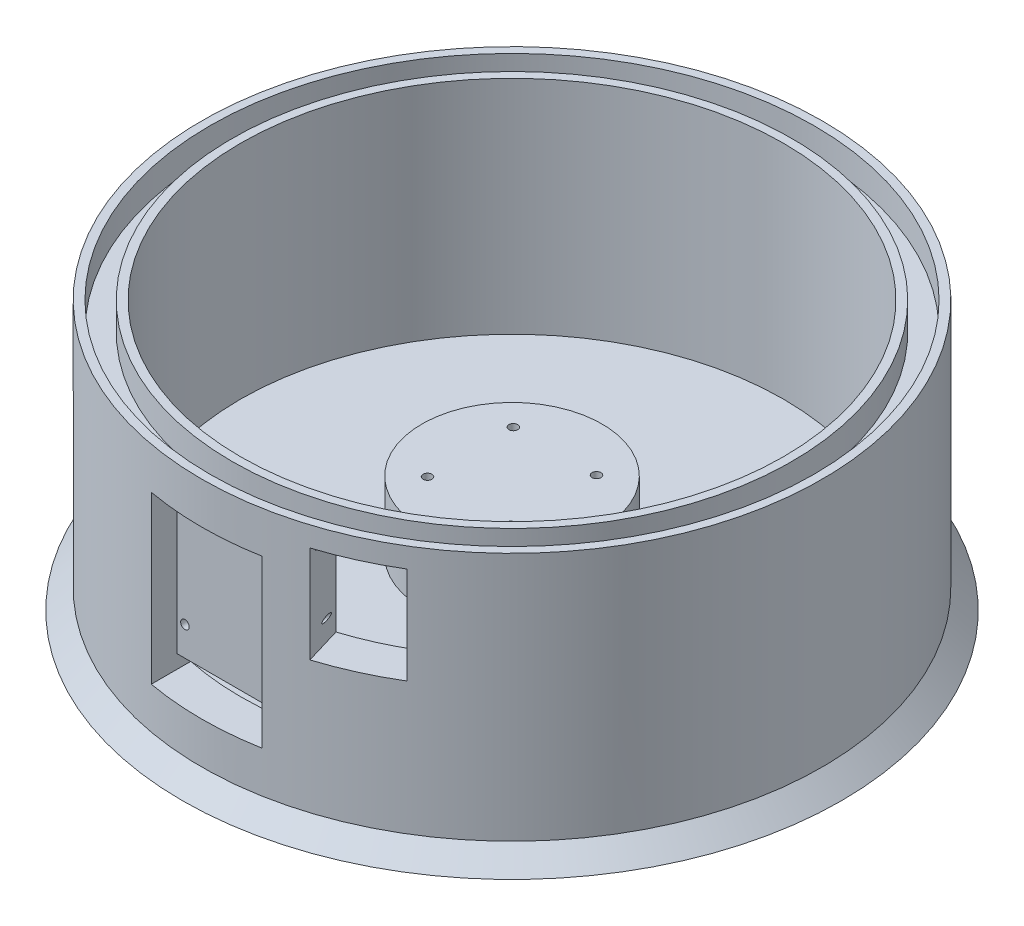
SolidWorks part; units mm, degrees
material "ABS"
ref_plane "Front Plane" through (0, 0, 0) normal (0, 0, 1) x (1, 0, 0)
ref_plane "Top Plane" through (0, 0, 0) normal (0, 1, 0) x (1, 0, 0)
ref_plane "Right Plane" through (0, 0, 0) normal (1, 0, 0) x (0, 0, -1)
sketch "Sketch1" plane through (0, 0, 0) normal (0, 1, 0) x (1, 0, 0)
  circle A1 centre (0, 0) radius 112
extrude "Boss-Extrude3" add sketch "Sketch1" along normal blind 90
ref_plane "Plane1" through (0, 0, 105) normal (0, 0, 1) x (1, 0, 0)
sketch "Sketch9" plane through (0, 90, 0) normal (0, 1, 0) x (1, 0, 0)
  circle A5 centre (0, 0) radius 101
  circle A7 centre (0, 0) radius 109
extrude "Cut-Extrude6" cut sketch "Sketch9" against normal blind 10
sketch "Sketch4" plane through (0, 0, 105) normal (0, 0, 1) x (1, 0, 0)
  line L26 (-20, 75) -> (20, 75)
  line L27 (-20, 75) -> (-20, 15)
  line L28 (-20, 15) -> (20, 15)
  line L29 (20, 75) -> (20, 15)
  line L30 (-20, 75) -> (20, 15) construction
  line L31 (-20, 15) -> (20, 75) construction
  point P0 (-0.4597, 42.5864)
  point P5 (0, 45)
  dimension "D1" = 60
  dimension "D2" = 40
  dimension "D3" = 45
extrude "Cut-Extrude2" cut sketch "Sketch4" along normal blind 26 and the other way blind 4
sketch "Sketch12" plane through (0, 0, 0) normal (0, -1, 0) x (1, 0, 0)
  circle A1 centre (0, 0) radius 112
  circle A2 centre (0, 0) radius 112
  dimension "D1" = 0
extrude "Boss-Extrude4" add sketch "Sketch12" along normal blind 7 draft 45 draft outward yes
sketch "Sketch13" plane through (0, 90, 0) normal (0, 1, 0) x (1, 0, 0)
  circle A0 centre (0, 0) radius 98
extrude "Cut-Extrude8" cut sketch "Sketch13" against normal blind 80 contours A0
sketch "Sketch14" plane through (0, 0, 101) normal (0, 0, 1) x (1, 0, 0)
  circle A0 centre (-31.25, 55.25) radius 0.75
  circle A1 centre (31.25, 55.25) radius 0.75
  circle A2 centre (31.25, 7.75) radius 0.75
  circle A3 centre (-31.25, 7.75) radius 0.75
extrude "Cut-Extrude9" cut sketch "Sketch14" against normal blind 15
sketch "Sketch18" plane through (0, 10, 0) normal (0, 1, 0) x (1, 0, 0)
  circle A0 centre (0, 0) radius 32.5
  dimension "D1" = 65
extrude "Boss-Extrude5" add sketch "Sketch18" along normal blind 25
sketch "Sketch16" plane through (0, -7, 0) normal (0, -1, 0) x (1, 0, 0)
  line L0 (0, 0) -> (-8.9936, 0) construction
  line L1 (0, 0) -> (0, 9.8047) construction
  circle A2 centre (-15, 15.5) radius 1.6
  circle A5 centre (15, 15.5) radius 1.6
  circle A6 centre (15, -15.5) radius 1.6
  circle A7 centre (-15, -15.5) radius 1.6
  point P2 (0, 0)
  dimension "D3" = 3.2
  dimension "D1" = 15.5
  dimension "D2" = 15
extrude "Cut-Extrude11" cut sketch "Sketch16" against normal through all
sketch "Sketch17" plane through (0, -7, 0) normal (0, -1, 0) x (1, 0, 0)
  circle A0 centre (-15, 15.5) radius 3
  circle A1 centre (15, 15.5) radius 3
  circle A2 centre (-15, -15.5) radius 3
  circle A3 centre (15, -15.5) radius 3
  dimension "D1" = 6
  dimension "D2" = 6
  dimension "D3" = 6
  dimension "D4" = 6
extrude "Cut-Extrude12" cut sketch "Sketch17" against normal blind 30
sketch "Sketch19" plane through (0, -7, 0) normal (0, -1, 0) x (1, 0, 0)
  circle A0 centre (0, 0) radius 30
  dimension "D1" = 60
extrude "Cut-Extrude13" cut sketch "Sketch19" against normal blind 25 contours A0
sketch "Sketch20" plane through (0, 0, 101) normal (0, 0, 1) x (1, 0, 0)
  line L0 (20, 75) -> (20, 15) construction
  line L1 (-20, 15) -> (20, 15)
  line L2 (-20, 15) -> (-20, 20)
  line L3 (-20, 20) -> (20, 20)
  line L4 (20, 15) -> (20, 20)
  dimension "D1" = 5
extrude "Cut-Extrude14" cut sketch "Sketch20" against normal blind 25
sketch "Sketch21" plane through (0, 0, 101) normal (0, 0, 1) x (1, 0, 0)
  line L0 (20, 75) -> (-20, 75) construction
  circle A0 centre (12.45, 67.8) radius 1.55
  circle A1 centre (-12.45, 67.8) radius 1.55
  circle A2 centre (-17.05, 30.54) radius 1.55
  circle A3 centre (17.05, 30.54) radius 1.55
  dimension "D3" = 3.1
  dimension "D4" = 3.1
  dimension "D9" = 3.1
  dimension "D10" = 3.1
  dimension "D1" = 12.45
  dimension "D2" = 24.9
  dimension "D5" = 7.2
  dimension "D6" = 7.2
  dimension "D7" = 17.05
  dimension "D8" = 17.05
  dimension "D11" = 37.26
  dimension "D12" = 37.26
extrude "Cut-Extrude15" cut sketch "Sketch21" against normal blind 25
ref_plane "Plane2" through (22.2041, 47.7941, -296.4042) normal (0, 1, 0) x (1, 0, 0)
sketch "Sketch22" plane through (22.2041, 47.7941, -296.4042) normal (0, 1, 0) x (1, 0, 0)
  line L0 (-5.1322, -347.3748) -> (12.405, -405.7625)
  line L1 (-5.1322, -347.3748) -> (4.3098, -343.0628)
  line L2 (4.3098, -343.0628) -> (37.058, -394.3842)
  line L3 (12.405, -405.7625) -> (37.058, -394.3842)
extrude "Cut-Extrude16" cut sketch "Sketch22" along normal blind 35
